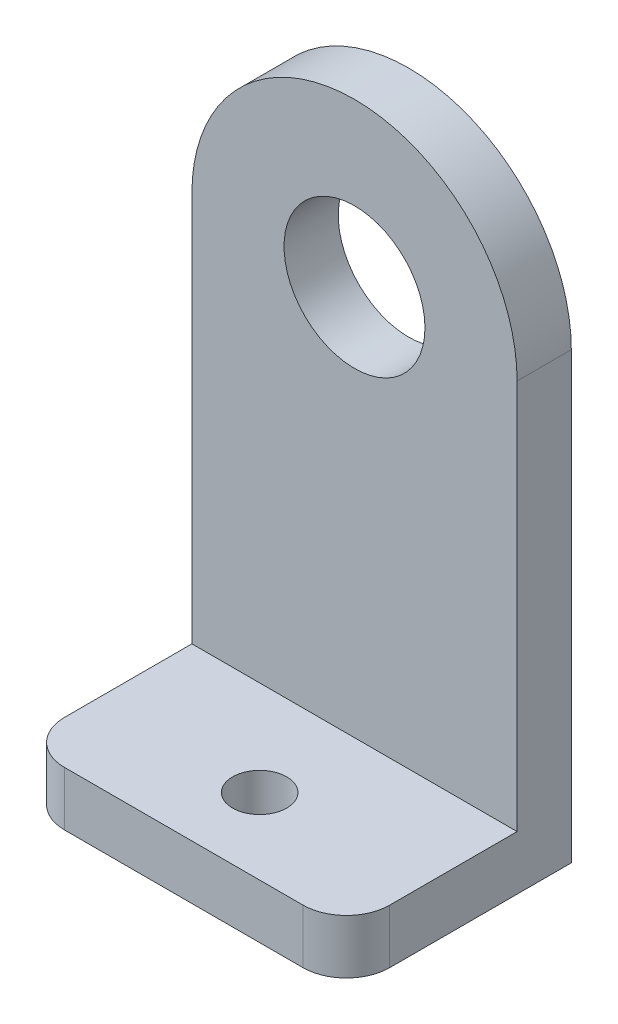
SolidWorks part; units mm, degrees
ref_plane "Front Plane" through (0, 0, 0) normal (0, 0, 1) x (1, 0, 0)
ref_plane "Top Plane" through (0, 0, 0) normal (0, 1, 0) x (1, 0, 0)
ref_plane "Right Plane" through (0, 0, 0) normal (1, 0, 0) x (0, 0, -1)
sketch "Sketch1" plane through (0, 0, 0) normal (0, 0, 1) x (1, 0, 0)
  line L0 (0, 0) -> (19.05, 0)
  line L1 (19.05, 0) -> (19.05, -45.72)
  line L2 (0, 0) -> (0, -5.8895)
  line L3 (19.05, -45.72) -> (-19.05, -45.72)
  line L4 (-19.05, -45.72) -> (-19.05, 0)
  line L5 (-19.05, 0) -> (0, 0)
  circle A0 centre (0, 0) radius 8.255
  circle A1 centre (0, 0) radius 19.05
  point P9 (0, -45.72)
  point P11 (-19.05, 0)
extrude "Boss-Extrude1" add sketch "Sketch1" along normal blind 6.35 contours L5 A1 L0 A0 | L0 A1 L5 A0 | A1 L4 L3 L1 region at (0, 9.1443, 0) region at (0, -9.1443, 0) region at (0, -30.047, 0)
sketch "Sketch2" plane through (0, -45.72, 0) normal (0, -1, 0) x (1, 0, 0)
  line L0 (-19.05, -17.4625) -> (-19.05, 23.8125)
  line L1 (-19.05, 6.35) -> (-19.05, 0) construction
  line L2 (-19.05, 23.8125) -> (19.05, 23.8125)
  line L3 (0, 23.8125) -> (0, 17.4625) construction
  line L4 (19.05, -17.4625) -> (19.05, 23.8125)
  line L5 (-19.05, 3.175) -> (-15.0266, 3.175) construction
  line L6 (-19.05, -17.4625) -> (19.05, -17.4625)
  circle A0 centre (0, 17.4625) radius 3.175
  circle A1 centre (0, -11.1125) radius 3.175
  point P15 (19.05, 3.175)
extrude "Boss-Extrude2" add sketch "Sketch2" along normal blind 3.175
sketch "Sketch4" plane through (0, 0, 23.8125) normal (0, 0, 1) x (1, 0, 0)
  line L0 (-19.05, -45.72) -> (19.05, -45.72)
  line L1 (19.05, -45.72) -> (19.05, -48.895)
  line L2 (19.05, -48.895) -> (-19.05, -48.895)
  line L3 (-19.05, -48.895) -> (-19.05, -45.72)
extrude "Boss-Extrude3" add sketch "Sketch4" along normal blind 2.54 contours L3 L0 L1 L2
ref_plane "Plane1" through (0, 0, 3.175) normal (0, 0, 1) x (1, 0, 0)
mirror "Mirror1" about plane through (0, 0, 3.175) normal (0, 0, 1) of "Boss-Extrude3"
sketch "Sketch5" plane through (0, -48.895, 0) normal (0, -1, 0) x (1, 0, 0)
  line L0 (-19.05, 26.3525) -> (19.05, 26.3525)
  line L1 (19.05, 26.3525) -> (19.05, -20.0025)
  line L2 (19.05, -20.0025) -> (-19.05, -20.0025)
  line L3 (-19.05, -20.0025) -> (-19.05, 26.3525)
extrude "Boss-Extrude4" add sketch "Sketch5" along normal blind 3.175
sketch "Sketch6" plane through (0, -45.72, 0) normal (0, 1, 0) x (1, 0, 0)
  circle A0 centre (0, 11.1125) radius 3.175
extrude "Cut-Extrude1" cut sketch "Sketch6" against normal blind 6.35
mirror "Mirror2" about plane through (0, 0, 3.175) normal (0, 0, 1) of "Cut-Extrude1"
fillet "Fillet1" radius 5.08 4 edges at (-19.05, -48.895, 26.3525) (19.05, -48.895, 26.3525) (-19.05, -48.895, -20.0025) (19.05, -48.895, -20.0025)
sketch "Sketch7" plane through (0, 0, -20.0025) normal (0, 0, -1) x (-1, 0, 0)
  line L1 (-36.2017, -39.8974) -> (34.1096, -39.8974)
  line L2 (-36.2017, -39.8974) -> (-36.2017, -55.3604)
  line L3 (-36.2017, -55.3604) -> (34.1096, -55.3604)
  line L4 (34.1096, -39.8974) -> (34.1096, -55.3604)
  line L5 (-1.046, -55.3604) -> (-1.046, -39.8974) construction
  line L6 (-36.2017, -47.6289) -> (34.1096, -47.6289) construction
  point P0 (-1.046, -47.6289)
extrude "Cut-Extrude2" cut sketch "Sketch7" against normal up to surface (20.0025 mm away) up to face at (8.255, 0, 0)
ref_axis "Axis1" through (0, 0, 6.35) along (0, 0, -1)
ref_axis "Axis2" through (0, -52.07, 17.4625) along (0, 1, 0)
